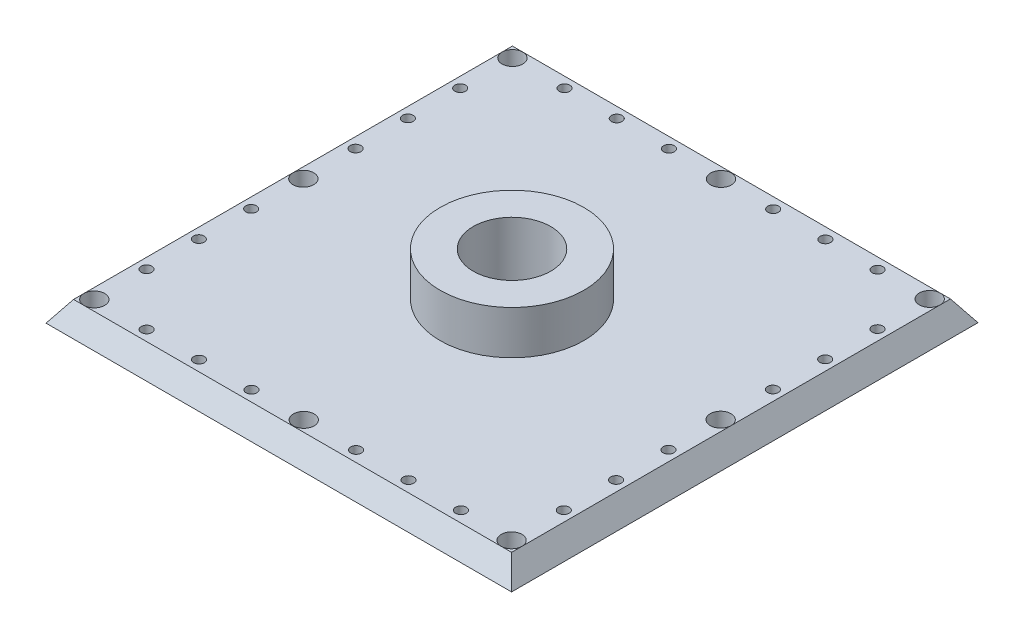
SolidWorks part; units mm, degrees
ref_plane "Alzado" through (0, 0, 0) normal (0, 0, 1) x (1, 0, 0)
ref_plane "Planta" through (0, 0, 0) normal (0, 1, 0) x (1, 0, 0)
ref_plane "Vista lateral" through (0, 0, 0) normal (1, 0, 0) x (0, 0, -1)
sketch "Croquis1" plane through (0, 0, 0) normal (0, 1, 0) x (1, 0, 0)
  line L0 (-113.25, 113.45) -> (113.25, 113.45)
  line L2 (-113.25, -113.45) -> (113.25, -113.45)
  line L3 (-113.25, 113.45) -> (-113.25, -113.45)
  line L4 (113.25, 113.45) -> (113.25, -113.45)
  circle A0 centre (0, 0) radius 18.85
  circle A1 centre (-101.5, 0) radius 5.05
  circle A2 centre (-101.5, -25.4) radius 2.6
  circle A3 centre (-101.5, -50.85) radius 2.6
  circle A4 centre (-101.5, -76.3) radius 2.6
  circle A5 centre (-101.5, -101.7) radius 5.05
  circle A6 centre (-101.5, 101.7) radius 5.05
  circle A7 centre (-101.5, 76.3) radius 2.6
  circle A8 centre (-101.5, 50.85) radius 2.6
  circle A9 centre (-101.5, 25.4) radius 2.6
  circle A10 centre (101.5, -101.7) radius 5.05
  circle A11 centre (101.5, -76.3) radius 2.6
  circle A12 centre (101.5, -50.85) radius 2.6
  circle A13 centre (101.5, -25.4) radius 2.6
  circle A14 centre (101.5, 0) radius 5.05
  circle A15 centre (101.5, 25.4) radius 2.6
  circle A16 centre (101.5, 50.85) radius 2.6
  circle A17 centre (101.5, 76.3) radius 2.6
  circle A18 centre (101.5, 101.7) radius 5.05
  circle A19 centre (76.4997, 101.3496) radius 2.6
  circle A20 centre (51.0497, 101.3997) radius 2.6
  circle A21 centre (25.5998, 101.4498) radius 2.6
  circle A22 centre (0.1998, 101.4998) radius 5.05
  circle A23 centre (-25.2001, 101.5498) radius 2.6
  circle A24 centre (-50.6501, 101.5999) radius 2.6
  circle A25 centre (-76.1, 101.65) radius 2.6
  circle A26 centre (76.4997, -101.3496) radius 2.6
  circle A27 centre (51.0497, -101.3997) radius 2.6
  circle A28 centre (25.5998, -101.4498) radius 2.6
  circle A29 centre (0.1998, -101.4998) radius 5.05
  circle A30 centre (-25.2001, -101.5498) radius 2.6
  circle A31 centre (-50.6501, -101.5999) radius 2.6
  circle A32 centre (-76.1, -101.65) radius 2.6
  dimension "D1" = 37.7
  dimension "D2" = 10.1
  dimension "D3" = 101.5
  dimension "D4" = 5.2
extrude "Saliente-Extruir1" add sketch "Croquis1" along normal blind 10
sketch "Croquis3" plane through (113.25, 0, 0) normal (1, 0, 0) x (0, 0, -1)
  line L0 (-113.45, 0) -> (-113.45, 10)
  line L1 (-113.45, 10) -> (-106.75, 10)
  line L3 (-113.45, 10) -> (113.45, 10) construction
  line L5 (-106.75, 10) -> (-113.45, 0)
extrude "Cortar-Extruir2" [suppressed] cut sketch "Croquis3" against normal blind 10 and the other way blind 226.5
chamfer "Chaflán1" distance 10 distance2 6.7 4 edges at (0, 10, -113.45) (113.25, 10, 0) (0, 10, 113.45) (-113.25, 10, 0) first distance on face at (0, 5, -113.45) first distance on face at (113.25, 5, 0) first distance on face at (0, 5, 113.45) first distance on face at (-113.25, 5, 0)
sketch "Croquis5" plane through (0, 10, 0) normal (0, 1, 0) x (1, 0, 0)
  circle A0 centre (0, 0) radius 34.95
  circle A1 centre (0, 0) radius 18.85
extrude "Saliente-Extruir7" add sketch "Croquis5" along normal blind 21.2
